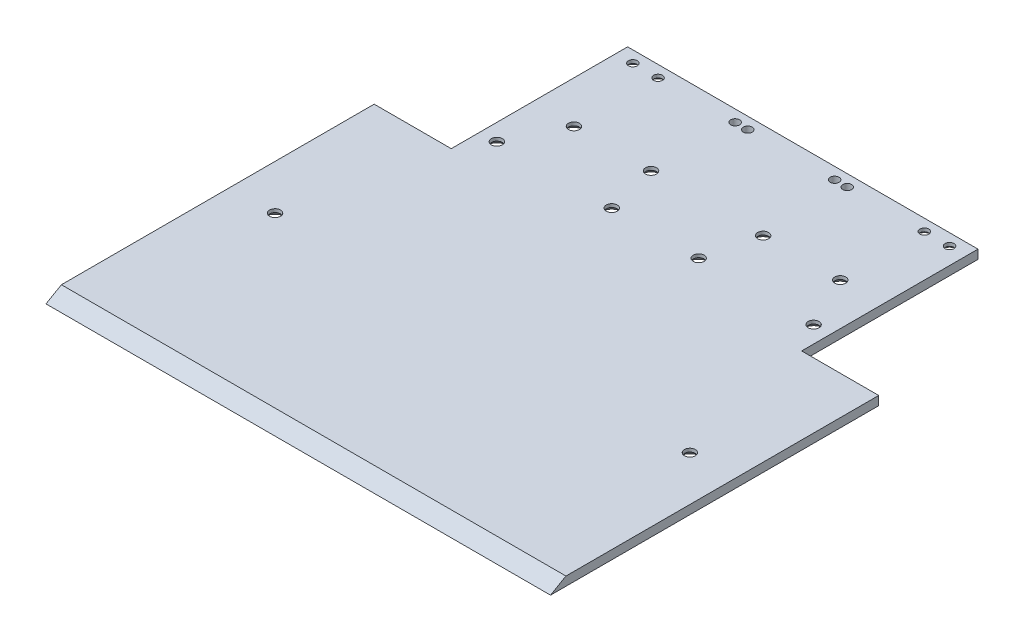
SolidWorks part; units mm, degrees
ref_plane "Alzado" through (0, 0, 0) normal (0, 0, 1) x (1, 0, 0)
ref_plane "Planta" through (0, 0, 0) normal (0, 1, 0) x (1, 0, 0)
ref_plane "Vista lateral" through (0, 0, 0) normal (1, 0, 0) x (0, 0, -1)
sketch "Croquis1" plane through (0, 0, 0) normal (0, 1, 0) x (1, 0, 0)
  line L0 (-62.5, 90) -> (-62.5, 27.08)
  line L1 (90, -90) -> (-90, -90)
  line L2 (90, -90) -> (90, 27.08)
  line L3 (62.5, 90) -> (-62.5, 90)
  line L4 (-90, -90) -> (-90, 27.08)
  line L5 (90, -90) -> (-62.5, 62.5) construction
  line L6 (62.5, 62.5) -> (-90, -90) construction
  line L7 (-62.5, 27.08) -> (-90, 27.08)
  line L8 (0, 90) -> (0, -90) construction
  line L9 (62.5, 27.08) -> (90, 27.08)
  line L10 (62.5, 90) -> (62.5, 27.08)
  point P0 (0, 0)
  dimension "D1" = 125
  dimension "D2" = 180
  dimension "D3" = 27.5
  dimension "D4" = 62.92
  dimension "D5" = 27.5
extrude "Saliente-Extruir1" add sketch "Croquis1" along normal blind 3.17
sketch "Croquis2" plane through (-90, 0, 0) normal (-1, 0, 0) x (0, 0, 1)
  line L0 (90, 0) -> (84.5094, 3.17)
  line L1 (-27.08, 3.17) -> (90, 3.17) construction
  line L2 (84.5094, 3.17) -> (90, 3.17)
  line L3 (90, 3.17) -> (90, 0)
  dimension "D1" = 60
extrude "Cortar-Extruir1" cut sketch "Croquis2" against normal up to next
sketch "Croquis3" plane through (0, 3.17, 0) normal (0, 1, 0) x (1, 0, 0)
  circle A0 centre (74, -24.2793) radius 1.585
extrude "Cortar-Extruir2" cut sketch "Croquis3" against normal up to next
mirror "Simetría1" about plane through (0, 0, 0) normal (1, 0, 0) of "Cortar-Extruir2"
sketch "Croquis4" plane through (0, 3.17, 0) normal (0, 1, 0) x (1, 0, 0)
  circle A0 centre (-56.5, 37.3511) radius 1.585
  circle A1 centre (-15.5, 37.3511) radius 1.585
  circle A2 centre (-15.5, 85.8511) radius 1.585
  circle A3 centre (-56.5, 85.8511) radius 1.585
extrude "Cortar-Extruir3" cut sketch "Croquis4" against normal up to next
sketch "Croquis6" plane through (0, 3.17, 0) normal (0, 1, 0) x (1, 0, 0)
  circle A0 centre (56.5, 85.8511) radius 1.585
  circle A1 centre (15.5, 85.8511) radius 1.585
  circle A2 centre (15.5, 37.3511) radius 1.585
  circle A3 centre (56.5, 37.3511) radius 1.585
extrude "Cortar-Extruir4" cut sketch "Croquis6" against normal up to next
sketch "Croquis7" plane through (0, 3.17, 0) normal (0, 1, 0) x (1, 0, 0)
  circle A0 centre (-20, 85.8511) radius 1.585
  circle A1 centre (-47.5, 85.8511) radius 1.585
  circle A2 centre (-47.5, 55.8511) radius 1.585
  circle A3 centre (-20, 55.8511) radius 1.585
extrude "Cortar-Extruir5" cut sketch "Croquis7" against normal up to next
mirror "Simetría2" about plane through (0, 0, 0) normal (1, 0, 0) of "Cortar-Extruir5"
sketch "Croquis15" plane through (0, 0, 0) normal (0, -1, 0) x (-1, 0, 0)
  circle A0 centre (20, 55.8511) radius 4
  circle A1 centre (15.5, 37.3511) radius 4
  circle A2 centre (56.5, 37.3511) radius 4
  circle A3 centre (47.5, 55.8511) radius 4
  circle A4 centre (56.5, 85.8511) radius 4
  circle A5 centre (47.5, 85.8511) radius 4
  circle A8 centre (74, -24.2793) radius 4
  dimension "D1" = 8
  dimension "D3" = 8
  dimension "D4" = 8
  dimension "D5" = 8
  dimension "D6" = 8
  dimension "D7" = 8
  dimension "D8" = 8
extrude "Cortar-Extruir6" cut sketch "Croquis15" against normal blind 2 draft 50.5
mirror "Simetría3" about plane through (0, 0, 0) normal (1, 0, 0) of "Cortar-Extruir6"
sketch "Croquis13" plane through (0, 0, 0) normal (0, -1, 0) x (-1, 0, 0)
  point P0 (-74, -24.2793)
  point P3 (-56.5, 37.3511)
  point P6 (-47.5, 55.8511)
  point P9 (-20, 55.8511)
  point P12 (-15.5, 37.3511)
  point P15 (15.5, 37.3511)
  point P18 (20, 55.8511)
  point P21 (47.5, 55.8511)
  point P24 (56.5, 37.3511)
  point P27 (74, -24.2793)
hole_wizard "Avellanado para tornillo con cabeza avellanada en cruz de M3.51" positions "Croquis13" profile "Croquis14" countersink size "M3.5" standard "AS" end condition through all
sketch "Croquis14" plane through (74, 0, 24.2793) normal (1, 0, 0) x (0, 0, -1)
  line L0 (0, 0) -> (0, 3.17)
  line L1 (0, 3.17) -> (1.95, 3.17)
  line L2 (1.95, 3.17) -> (1.95, 1.9797)
  line L3 (1.95, 1.9797) -> (4, 0)
  line L5 (4, 0) -> (0, 0)
  line L6 (-1.95, 1.9797) -> (-4, 0) construction
  line L11 (0, -6.35) -> (0, 107.95) construction
  dimension "Diámetro de taladro hasta el siguiente" = 3.9
  dimension "Profundidad de taladro hasta el siguiente" = 3.17
  dimension "Diámetro de avellanado cercano" = 8
  dimension "Ángulo de avellanado cercano" = 92
